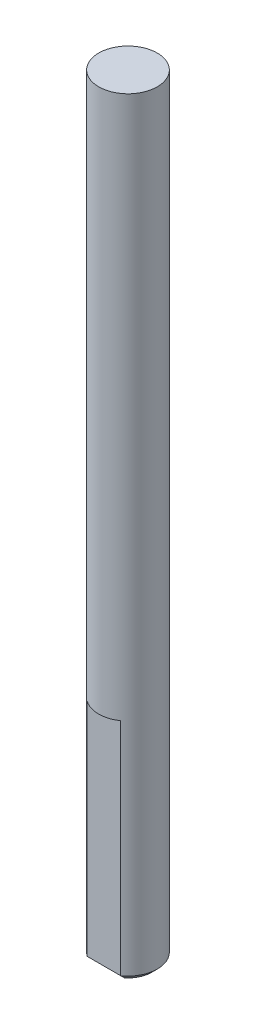
SolidWorks part; units mm, degrees
ref_plane "Front Plane" through (0, 0, 0) normal (0, 0, 1) x (1, 0, 0)
ref_plane "Top Plane" through (0, 0, 0) normal (0, 1, 0) x (1, 0, 0)
ref_plane "Right Plane" through (0, 0, 0) normal (1, 0, 0) x (0, 0, -1)
sketch "Sketch1" plane through (0, 0, 0) normal (0, 1, 0) x (1, 0, 0)
  line L0 (-1.5, -2.1542) -> (1.5, -2.1542)
  circle A0 centre (0, 0) radius 2.625
  dimension "D1" = 5.25
  dimension "D2" = 3
extrude "Boss-Extrude1" add sketch "Sketch1" along normal blind 69 contours L0 A0 | L0 A0 region at (0, 0, -0.1088) region at (0, 0, 2.3441)
extrude "Cut-Extrude1" cut sketch "Sketch1<3>" along normal blind 20.3 contours L0 A0 region at (0, 0, 2.3441)
sketch "Sketch1<3>" plane through (0, 0, 0) normal (0, 1, 0) x (1, 0, 0) same geometry as "Sketch1"
chamfer "Chamfer1" distance 0.5 angle 45 2 edges at (0, 0, 2.1542) (0, 0, -2.625) tangent propagation no
